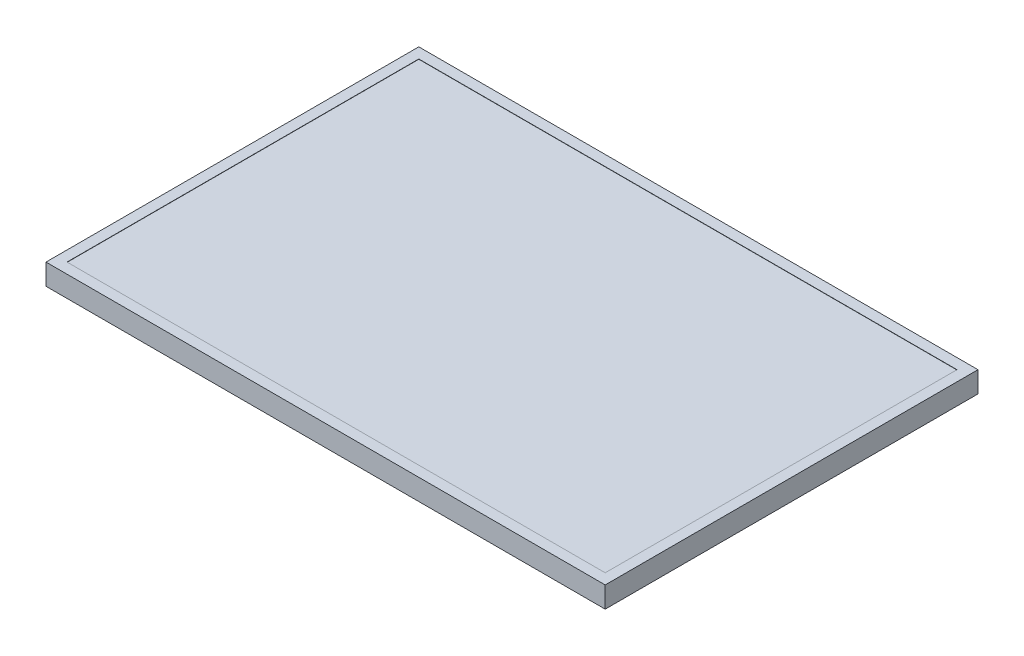
SolidWorks part; units mm, degrees
ref_plane "Front Plane" through (0, 0, 0) normal (0, 0, 1) x (1, 0, 0)
ref_plane "Top Plane" through (0, 0, 0) normal (0, 1, 0) x (1, 0, 0)
ref_plane "Right Plane" through (0, 0, 0) normal (1, 0, 0) x (0, 0, -1)
sketch "Sketch1" plane through (0, 0, 0) normal (0, 1, 0) x (1, 0, 0)
  line L1 (-512.5, -335) -> (512.5, -335)
  line L2 (-512.5, -335) -> (-512.5, 335)
  line L3 (-512.5, 335) -> (512.5, 335)
  line L4 (512.5, -335) -> (512.5, 335)
  line L5 (-512.5, -335) -> (512.5, 335) construction
  line L6 (-512.5, 335) -> (512.5, -335) construction
  point P0 (0, 0)
  dimension "D1" = 670
  dimension "D2" = 1025
extrude "Boss-Extrude1" add sketch "Sketch1" along normal blind 15
sketch "Sketch2" plane through (0, 15, 0) normal (0, 1, 0) x (1, 0, 0)
  line L0 (512.5, 335) -> (-512.5, 335) construction
  line L1 (-468.5, 318) -> (-332.5, 318)
  line L2 (-478.5, 308) -> (-478.5, 172)
  line L3 (-468.5, 162) -> (-332.5, 162)
  line L4 (-322.5, 308) -> (-322.5, 172)
  line L5 (-512.5, 335) -> (-512.5, -335) construction
  line L6 (-478.5, 308) -> (-468.5, 318)
  line L7 (-478.5, 172) -> (-468.5, 162)
  line L8 (-332.5, 162) -> (-322.5, 172)
  line L9 (-332.5, 318) -> (-322.5, 308)
  line L10 (-308.5, 318) -> (-172.5, 318)
  line L11 (-318.5, 308) -> (-318.5, 172)
  line L12 (-308.5, 162) -> (-172.5, 162)
  line L13 (-162.5, 308) -> (-162.5, 172)
  line L14 (-318.5, 308) -> (-308.5, 318)
  line L15 (-318.5, 172) -> (-308.5, 162)
  line L16 (-172.5, 162) -> (-162.5, 172)
  line L17 (-172.5, 318) -> (-162.5, 308)
  line L18 (-148.5, 318) -> (-12.5, 318)
  line L19 (-158.5, 308) -> (-158.5, 172)
  line L20 (-148.5, 162) -> (-12.5, 162)
  line L21 (-2.5, 308) -> (-2.5, 172)
  line L22 (-158.5, 308) -> (-148.5, 318)
  line L23 (-158.5, 172) -> (-148.5, 162)
  line L24 (-12.5, 162) -> (-2.5, 172)
  line L25 (-12.5, 318) -> (-2.5, 308)
  line L26 (11.5, 318) -> (147.5, 318)
  line L27 (1.5, 308) -> (1.5, 172)
  line L28 (11.5, 162) -> (147.5, 162)
  line L29 (157.5, 308) -> (157.5, 172)
  line L30 (1.5, 308) -> (11.5, 318)
  line L31 (1.5, 172) -> (11.5, 162)
  line L32 (147.5, 162) -> (157.5, 172)
  line L33 (147.5, 318) -> (157.5, 308)
  line L34 (171.5, 318) -> (307.5, 318)
  line L35 (161.5, 308) -> (161.5, 172)
  line L36 (171.5, 162) -> (307.5, 162)
  line L37 (317.5, 308) -> (317.5, 172)
  line L38 (161.5, 308) -> (171.5, 318)
  line L39 (161.5, 172) -> (171.5, 162)
  line L40 (307.5, 162) -> (317.5, 172)
  line L41 (307.5, 318) -> (317.5, 308)
  line L42 (331.5, 318) -> (467.5, 318)
  line L43 (321.5, 308) -> (321.5, 172)
  line L44 (331.5, 162) -> (467.5, 162)
  line L45 (477.5, 308) -> (477.5, 172)
  line L46 (321.5, 308) -> (331.5, 318)
  line L47 (321.5, 172) -> (331.5, 162)
  line L48 (467.5, 162) -> (477.5, 172)
  line L49 (467.5, 318) -> (477.5, 308)
  line L50 (-308.5, 158) -> (-172.5, 158)
  line L51 (-318.5, 148) -> (-318.5, 12)
  line L52 (-308.5, 2) -> (-172.5, 2)
  line L53 (-162.5, 148) -> (-162.5, 12)
  line L54 (-318.5, 148) -> (-308.5, 158)
  line L55 (-318.5, 12) -> (-308.5, 2)
  line L56 (-172.5, 2) -> (-162.5, 12)
  line L57 (-172.5, 158) -> (-162.5, 148)
  line L58 (-148.5, 158) -> (-12.5, 158)
  line L59 (-158.5, 148) -> (-158.5, 12)
  line L60 (-148.5, 2) -> (-12.5, 2)
  line L61 (-2.5, 148) -> (-2.5, 12)
  line L62 (-158.5, 148) -> (-148.5, 158)
  line L63 (-158.5, 12) -> (-148.5, 2)
  line L64 (-12.5, 2) -> (-2.5, 12)
  line L65 (-12.5, 158) -> (-2.5, 148)
  line L66 (11.5, 158) -> (147.5, 158)
  line L67 (1.5, 148) -> (1.5, 12)
  line L68 (11.5, 2) -> (147.5, 2)
  line L69 (157.5, 148) -> (157.5, 12)
  line L70 (1.5, 148) -> (11.5, 158)
  line L71 (1.5, 12) -> (11.5, 2)
  line L72 (147.5, 2) -> (157.5, 12)
  line L73 (147.5, 158) -> (157.5, 148)
  line L74 (171.5, 158) -> (307.5, 158)
  line L75 (161.5, 148) -> (161.5, 12)
  line L76 (171.5, 2) -> (307.5, 2)
  line L77 (317.5, 148) -> (317.5, 12)
  line L78 (161.5, 148) -> (171.5, 158)
  line L79 (161.5, 12) -> (171.5, 2)
  line L80 (307.5, 2) -> (317.5, 12)
  line L81 (307.5, 158) -> (317.5, 148)
  line L82 (331.5, 158) -> (467.5, 158)
  line L83 (321.5, 148) -> (321.5, 12)
  line L84 (331.5, 2) -> (467.5, 2)
  line L85 (477.5, 148) -> (477.5, 12)
  line L86 (321.5, 148) -> (331.5, 158)
  line L87 (321.5, 12) -> (331.5, 2)
  line L88 (467.5, 2) -> (477.5, 12)
  line L89 (467.5, 158) -> (477.5, 148)
  line L90 (-308.5, -2) -> (-172.5, -2)
  line L91 (-318.5, -12) -> (-318.5, -148)
  line L92 (-308.5, -158) -> (-172.5, -158)
  line L93 (-162.5, -12) -> (-162.5, -148)
  line L94 (-318.5, -12) -> (-308.5, -2)
  line L95 (-318.5, -148) -> (-308.5, -158)
  line L96 (-172.5, -158) -> (-162.5, -148)
  line L97 (-172.5, -2) -> (-162.5, -12)
  line L98 (-148.5, -2) -> (-12.5, -2)
  line L99 (-158.5, -12) -> (-158.5, -148)
  line L100 (-148.5, -158) -> (-12.5, -158)
  line L101 (-2.5, -12) -> (-2.5, -148)
  line L102 (-158.5, -12) -> (-148.5, -2)
  line L103 (-158.5, -148) -> (-148.5, -158)
  line L104 (-12.5, -158) -> (-2.5, -148)
  line L105 (-12.5, -2) -> (-2.5, -12)
  line L106 (11.5, -2) -> (147.5, -2)
  line L107 (1.5, -12) -> (1.5, -148)
  line L108 (11.5, -158) -> (147.5, -158)
  line L109 (157.5, -12) -> (157.5, -148)
  line L110 (1.5, -12) -> (11.5, -2)
  line L111 (1.5, -148) -> (11.5, -158)
  line L112 (147.5, -158) -> (157.5, -148)
  line L113 (147.5, -2) -> (157.5, -12)
  line L114 (171.5, -2) -> (307.5, -2)
  line L115 (161.5, -12) -> (161.5, -148)
  line L116 (171.5, -158) -> (307.5, -158)
  line L117 (317.5, -12) -> (317.5, -148)
  line L118 (161.5, -12) -> (171.5, -2)
  line L119 (161.5, -148) -> (171.5, -158)
  line L120 (307.5, -158) -> (317.5, -148)
  line L121 (307.5, -2) -> (317.5, -12)
  line L122 (331.5, -2) -> (467.5, -2)
  line L123 (321.5, -12) -> (321.5, -148)
  line L124 (331.5, -158) -> (467.5, -158)
  line L125 (477.5, -12) -> (477.5, -148)
  line L126 (321.5, -12) -> (331.5, -2)
  line L127 (321.5, -148) -> (331.5, -158)
  line L128 (467.5, -158) -> (477.5, -148)
  line L129 (467.5, -2) -> (477.5, -12)
  line L130 (-308.5, -162) -> (-172.5, -162)
  line L131 (-318.5, -172) -> (-318.5, -308)
  line L132 (-308.5, -318) -> (-172.5, -318)
  line L133 (-162.5, -172) -> (-162.5, -308)
  line L134 (-318.5, -172) -> (-308.5, -162)
  line L135 (-318.5, -308) -> (-308.5, -318)
  line L136 (-172.5, -318) -> (-162.5, -308)
  line L137 (-172.5, -162) -> (-162.5, -172)
  line L138 (-148.5, -162) -> (-12.5, -162)
  line L139 (-158.5, -172) -> (-158.5, -308)
  line L140 (-148.5, -318) -> (-12.5, -318)
  line L141 (-2.5, -172) -> (-2.5, -308)
  line L142 (-158.5, -172) -> (-148.5, -162)
  line L143 (-158.5, -308) -> (-148.5, -318)
  line L144 (-12.5, -318) -> (-2.5, -308)
  line L145 (-12.5, -162) -> (-2.5, -172)
  line L146 (11.5, -162) -> (147.5, -162)
  line L147 (1.5, -172) -> (1.5, -308)
  line L148 (11.5, -318) -> (147.5, -318)
  line L149 (157.5, -172) -> (157.5, -308)
  line L150 (1.5, -172) -> (11.5, -162)
  line L151 (1.5, -308) -> (11.5, -318)
  line L152 (147.5, -318) -> (157.5, -308)
  line L153 (147.5, -162) -> (157.5, -172)
  line L154 (171.5, -162) -> (307.5, -162)
  line L155 (161.5, -172) -> (161.5, -308)
  line L156 (171.5, -318) -> (307.5, -318)
  line L157 (317.5, -172) -> (317.5, -308)
  line L158 (161.5, -172) -> (171.5, -162)
  line L159 (161.5, -308) -> (171.5, -318)
  line L160 (307.5, -318) -> (317.5, -308)
  line L161 (307.5, -162) -> (317.5, -172)
  line L162 (331.5, -162) -> (467.5, -162)
  line L163 (321.5, -172) -> (321.5, -308)
  line L164 (331.5, -318) -> (467.5, -318)
  line L165 (477.5, -172) -> (477.5, -308)
  line L166 (321.5, -172) -> (331.5, -162)
  line L167 (321.5, -308) -> (331.5, -318)
  line L168 (467.5, -318) -> (477.5, -308)
  line L169 (467.5, -162) -> (477.5, -172)
  line L170 (-468.5, 158) -> (-332.5, 158)
  line L171 (-478.5, 148) -> (-478.5, 12)
  line L172 (-468.5, 2) -> (-332.5, 2)
  line L173 (-322.5, 148) -> (-322.5, 12)
  line L174 (-478.5, 148) -> (-468.5, 158)
  line L175 (-478.5, 12) -> (-468.5, 2)
  line L176 (-332.5, 2) -> (-322.5, 12)
  line L177 (-332.5, 158) -> (-322.5, 148)
  line L178 (-468.5, -2) -> (-332.5, -2)
  line L179 (-478.5, -12) -> (-478.5, -148)
  line L180 (-468.5, -158) -> (-332.5, -158)
  line L181 (-322.5, -12) -> (-322.5, -148)
  line L182 (-478.5, -12) -> (-468.5, -2)
  line L183 (-478.5, -148) -> (-468.5, -158)
  line L184 (-332.5, -158) -> (-322.5, -148)
  line L185 (-332.5, -2) -> (-322.5, -12)
  line L186 (-468.5, -162) -> (-332.5, -162)
  line L187 (-478.5, -172) -> (-478.5, -308)
  line L188 (-468.5, -318) -> (-332.5, -318)
  line L189 (-322.5, -172) -> (-322.5, -308)
  line L190 (-478.5, -172) -> (-468.5, -162)
  line L191 (-478.5, -308) -> (-468.5, -318)
  line L192 (-332.5, -318) -> (-322.5, -308)
  line L193 (-332.5, -162) -> (-322.5, -172)
  point P0 (-478.5, 318)
  point P1 (-322.5, 162)
  point P2 (-478.5, 162)
  point P3 (-322.5, 318)
  point P19 (-318.5, 318)
  point P20 (-162.5, 162)
  point P21 (-318.5, 162)
  point P22 (-162.5, 318)
  point P31 (-158.5, 318)
  point P32 (-2.5, 162)
  point P33 (-158.5, 162)
  point P34 (-2.5, 318)
  point P43 (1.5, 318)
  point P44 (157.5, 162)
  point P45 (1.5, 162)
  point P46 (157.5, 318)
  point P55 (161.5, 318)
  point P56 (317.5, 162)
  point P57 (161.5, 162)
  point P58 (317.5, 318)
  point P67 (321.5, 318)
  point P68 (477.5, 162)
  point P69 (321.5, 162)
  point P70 (477.5, 318)
  point P79 (-318.5, 158)
  point P80 (-162.5, 2)
  point P81 (-318.5, 2)
  point P82 (-162.5, 158)
  point P91 (-158.5, 158)
  point P92 (-2.5, 2)
  point P93 (-158.5, 2)
  point P94 (-2.5, 158)
  point P103 (1.5, 158)
  point P104 (157.5, 2)
  point P105 (1.5, 2)
  point P106 (157.5, 158)
  point P115 (161.5, 158)
  point P116 (317.5, 2)
  point P117 (161.5, 2)
  point P118 (317.5, 158)
  point P127 (321.5, 158)
  point P128 (477.5, 2)
  point P129 (321.5, 2)
  point P130 (477.5, 158)
  point P139 (-318.5, -2)
  point P140 (-162.5, -158)
  point P141 (-318.5, -158)
  point P142 (-162.5, -2)
  point P151 (-158.5, -2)
  point P152 (-2.5, -158)
  point P153 (-158.5, -158)
  point P154 (-2.5, -2)
  point P163 (1.5, -2)
  point P164 (157.5, -158)
  point P165 (1.5, -158)
  point P166 (157.5, -2)
  point P175 (161.5, -2)
  point P176 (317.5, -158)
  point P177 (161.5, -158)
  point P178 (317.5, -2)
  point P187 (321.5, -2)
  point P188 (477.5, -158)
  point P189 (321.5, -158)
  point P190 (477.5, -2)
  point P199 (-318.5, -162)
  point P200 (-162.5, -318)
  point P201 (-318.5, -318)
  point P202 (-162.5, -162)
  point P211 (-158.5, -162)
  point P212 (-2.5, -318)
  point P213 (-158.5, -318)
  point P214 (-2.5, -162)
  point P223 (1.5, -162)
  point P224 (157.5, -318)
  point P225 (1.5, -318)
  point P226 (157.5, -162)
  point P235 (161.5, -162)
  point P236 (317.5, -318)
  point P237 (161.5, -318)
  point P238 (317.5, -162)
  point P247 (321.5, -162)
  point P248 (477.5, -318)
  point P249 (321.5, -318)
  point P250 (477.5, -162)
  point P259 (-478.5, 158)
  point P260 (-322.5, 2)
  point P261 (-478.5, 2)
  point P262 (-322.5, 158)
  point P271 (-478.5, -2)
  point P272 (-322.5, -158)
  point P273 (-478.5, -158)
  point P274 (-322.5, -2)
  point P283 (-478.5, -162)
  point P284 (-322.5, -318)
  point P285 (-478.5, -318)
  point P286 (-322.5, -162)
  dimension "D1" = 17
  dimension "D2" = 34
  dimension "D3" = 156
  dimension "D4" = 156
  dimension "D5" = 6
  dimension "D6" = 4
extrude "Boss-Extrude2" add sketch "Sketch2" along normal blind 0.5 separate body
sketch "Sketch3" plane through (0, 15.5, 0) normal (0, 1, 0) x (1, 0, 0)
  line L0 (-332.5, 318) -> (-468.5, 318) construction
  line L1 (-456.5, 318) -> (-455.5, 318)
  line L2 (-456.5, 318) -> (-456.5, 162)
  line L3 (-456.5, 162) -> (-455.5, 162)
  line L4 (-455.5, 318) -> (-455.5, 162)
  line L5 (-468.5, 162) -> (-332.5, 162) construction
  line L6 (-478.5, 308) -> (-478.5, 172) construction
  line L7 (-446.5, 318) -> (-445.5, 318)
  line L8 (-446.5, 318) -> (-446.5, 162)
  line L9 (-446.5, 162) -> (-445.5, 162)
  line L10 (-445.5, 318) -> (-445.5, 162)
  line L11 (-436.5, 318) -> (-435.5, 318)
  line L12 (-436.5, 318) -> (-436.5, 162)
  line L13 (-436.5, 162) -> (-435.5, 162)
  line L14 (-435.5, 318) -> (-435.5, 162)
  line L15 (-426.5, 318) -> (-425.5, 318)
  line L16 (-426.5, 318) -> (-426.5, 162)
  line L17 (-426.5, 162) -> (-425.5, 162)
  line L18 (-425.5, 318) -> (-425.5, 162)
  line L19 (-416.5, 318) -> (-415.5, 318)
  line L20 (-416.5, 318) -> (-416.5, 162)
  line L21 (-416.5, 162) -> (-415.5, 162)
  line L22 (-415.5, 318) -> (-415.5, 162)
  line L23 (-406.5, 318) -> (-405.5, 318)
  line L24 (-406.5, 318) -> (-406.5, 162)
  line L25 (-406.5, 162) -> (-405.5, 162)
  line L26 (-405.5, 318) -> (-405.5, 162)
  line L27 (-396.5, 318) -> (-395.5, 318)
  line L28 (-396.5, 318) -> (-396.5, 162)
  line L29 (-396.5, 162) -> (-395.5, 162)
  line L30 (-395.5, 318) -> (-395.5, 162)
  line L31 (-386.5, 318) -> (-385.5, 318)
  line L32 (-386.5, 318) -> (-386.5, 162)
  line L33 (-386.5, 162) -> (-385.5, 162)
  line L34 (-385.5, 318) -> (-385.5, 162)
  line L35 (-376.5, 318) -> (-375.5, 318)
  line L36 (-376.5, 318) -> (-376.5, 162)
  line L37 (-376.5, 162) -> (-375.5, 162)
  line L38 (-375.5, 318) -> (-375.5, 162)
  line L39 (-366.5, 318) -> (-365.5, 318)
  line L40 (-366.5, 318) -> (-366.5, 162)
  line L41 (-366.5, 162) -> (-365.5, 162)
  line L42 (-365.5, 318) -> (-365.5, 162)
  line L43 (-356.5, 318) -> (-355.5, 318)
  line L44 (-356.5, 318) -> (-356.5, 162)
  line L45 (-356.5, 162) -> (-355.5, 162)
  line L46 (-355.5, 318) -> (-355.5, 162)
  line L47 (-346.5, 318) -> (-345.5, 318)
  line L48 (-346.5, 318) -> (-346.5, 162)
  line L49 (-346.5, 162) -> (-345.5, 162)
  line L50 (-345.5, 318) -> (-345.5, 162)
  dimension "D1" = 22
  dimension "D2" = 1
  dimension "D3" = 12
extrude "Boss-Extrude3" add sketch "Sketch3" along normal blind 0.5 separate body
pattern_linear "LPattern1" count 6 spacing 160 along (1, 0, 0) count 4 spacing 160 along (0, 0, 1) of "Boss-Extrude3"
sketch "Sketch4" plane through (0, 16, 0) normal (0, 1, 0) x (1, 0, 0)
  line L0 (-478.5, 308) -> (-478.5, 172) construction
  line L1 (-478.5, 281) -> (500.5, 281)
  line L2 (-478.5, 281) -> (-478.5, 276)
  line L3 (-478.5, 276) -> (500.5, 276)
  line L6 (512.5, 335) -> (-512.5, 335) construction
  line L8 (500.5, 281) -> (500.5, 276)
  line L9 (512.5, -335) -> (512.5, 335) construction
  line L10 (-478.5, 201) -> (500.5, 201)
  line L11 (-478.5, 201) -> (-478.5, 196)
  line L12 (-478.5, 196) -> (500.5, 196)
  line L13 (500.5, 201) -> (500.5, 196)
  dimension "D1" = 5
  dimension "D2" = 54
  dimension "D3" = 12
  dimension "D4" = 2
extrude "Boss-Extrude4" add sketch "Sketch4" along normal blind 0.5 separate body
pattern_linear "LPattern2" count 4 spacing 160 along (0, 0, 1) of "Boss-Extrude4"
sketch "Sketch5" plane through (0, 15, 0) normal (0, 1, 0) x (1, 0, 0)
  line L0 (512.5, 335) -> (-512.5, 335) construction
  line L1 (486.5, 324) -> (500.5, 324)
  line L2 (486.5, 324) -> (486.5, -324)
  line L3 (486.5, -324) -> (500.5, -324)
  line L4 (500.5, 324) -> (500.5, -324)
  line L5 (512.5, -335) -> (512.5, 335) construction
  line L6 (-512.5, -335) -> (512.5, -335) construction
  dimension "D1" = 14
  dimension "D2" = 11
  dimension "D3" = 12
  dimension "D4" = 11
extrude "Boss-Extrude5" add sketch "Sketch5" along normal blind 1.5
sketch "Sketch6" plane through (0, 16.5, 0) normal (0, 1, 0) x (1, 0, 0)
  line L1 (-512.5, 335) -> (512.5, 335)
  line L2 (-512.5, 335) -> (-512.5, -335)
  line L3 (-512.5, -335) -> (512.5, -335)
  line L4 (512.5, 335) -> (512.5, -335)
extrude "Boss-Extrude6" add sketch "Sketch6" along normal blind 3 separate body
sketch "Sketch7" plane through (0, 15, 0) normal (0, 1, 0) x (1, 0, 0)
  line L1 (-512.5, 335) -> (512.5, 335)
  line L2 (-512.5, 335) -> (-512.5, -335)
  line L3 (-512.5, -335) -> (512.5, -335)
  line L4 (512.5, 335) -> (512.5, -335)
  line L5 (-532.5, 355) -> (532.5, 355)
  line L6 (-532.5, 355) -> (-532.5, -355)
  line L7 (-532.5, -355) -> (532.5, -355)
  line L8 (532.5, 355) -> (532.5, -355)
  dimension "D1" = 20
  dimension "D2" = 20
  dimension "D3" = 20
  dimension "D4" = 20
extrude "Boss-Extrude7" add sketch "Sketch7" along normal blind 5 and the other way blind 35 separate body
